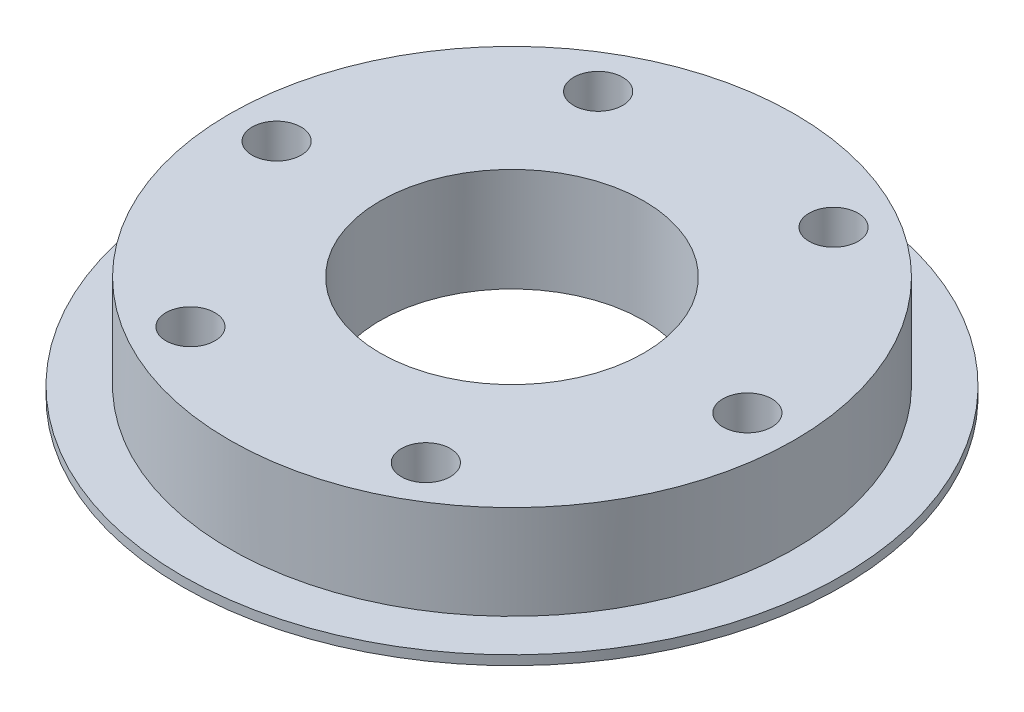
SolidWorks part; units mm, degrees
ref_plane "Front Plane" through (0, 0, 0) normal (0, 0, 1) x (1, 0, 0)
ref_plane "Top Plane" through (0, 0, 0) normal (0, 1, 0) x (1, 0, 0)
ref_plane "Right Plane" through (0, 0, 0) normal (1, 0, 0) x (0, 0, -1)
sketch "Sketch1" plane through (0, 0, 0) normal (0, 1, 0) x (1, 0, 0)
  circle A0 centre (0, 0) radius 30
  point P18 (0, 0)
  dimension "D4" = 60
extrude "Boss-Extrude1" add sketch "Sketch1" along normal blind 11
sketch "Sketch2" plane through (0, 0, 0) normal (0, -1, 0) x (1, 0, 0)
  circle A0 centre (0, 0) radius 35
  dimension "D1" = 70
extrude "Boss-Extrude2" add sketch "Sketch2" against normal blind 1
sketch "Sketch3" plane through (0, 0, 0) normal (0, 1, 0) x (1, 0, 0)
  circle A1 centre (0, 0) radius 25 construction
  circle A2 centre (0, 25) radius 1.75
  circle A3 centre (21.6506, 12.5) radius 1.75
  circle A4 centre (21.6506, -12.5) radius 1.75
  circle A5 centre (0, -25) radius 1.75
  circle A6 centre (-21.6506, -12.5) radius 1.75
  circle A7 centre (-21.6506, 12.5) radius 1.75
  point P30 (0, 0)
  dimension "D1" = 50
  dimension "D2" = 3.5
  dimension "D3" = 6
extrude "Cut-Extrude1" cut sketch "Sketch3" along normal blind 4
sketch "Sketch4" plane through (0, 0, 0) normal (0, -1, 0) x (1, 0, 0)
  circle A0 centre (0, 0) radius 14
  dimension "D1" = 28
extrude "Cut-Extrude2" cut sketch "Sketch4" against normal blind 51
sketch "Sketch5" plane through (0, 0, 0) normal (0, -1, 0) x (1, 0, 0)
  line L0 (-12.5, 21.6506) -> (0, 0) construction
  line L1 (0, 0) -> (0, 25) construction
  line L2 (0, 25) -> (-21.6506, 12.5) construction
  circle A0 centre (0, 0) radius 25 construction
  circle A1 centre (-12.5, 21.6506) radius 2.6
  circle A2 centre (12.5, 21.6506) radius 2.6
  circle A3 centre (25, 0) radius 2.6
  circle A4 centre (12.5, -21.6506) radius 2.6
  circle A5 centre (-12.5, -21.6506) radius 2.6
  circle A6 centre (-25, 0) radius 2.6
  point P21 (0, 0)
  dimension "D1" = 5.2
  dimension "D2" = 6
extrude "Cut-Extrude3" cut sketch "Sketch5" against normal blind 25
